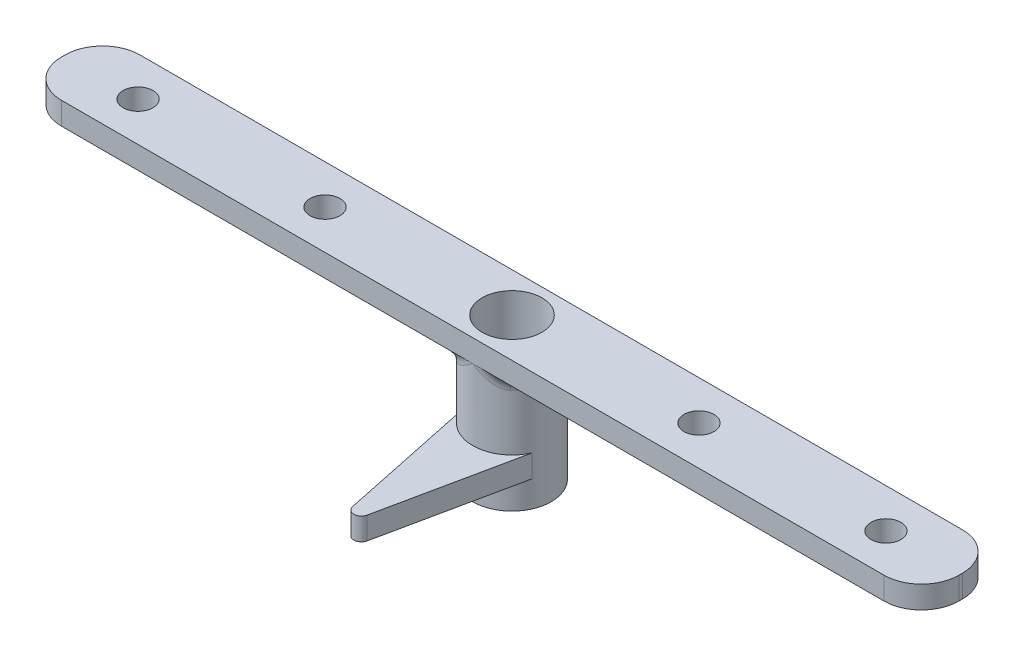
SolidWorks part; units mm, degrees
ref_plane "Front Plane" through (0, 0, 0) normal (0, 0, 1) x (1, 0, 0)
ref_plane "Top Plane" through (0, 0, 0) normal (0, 1, 0) x (1, 0, 0)
ref_plane "Right Plane" through (0, 0, 0) normal (1, 0, 0) x (0, 0, -1)
sketch "Sketch2" plane through (0, 0, 0) normal (1, 0, 0) x (0, 0, -1)
  line L0 (0, 0) -> (5.25, 0)
  line L1 (5.25, 0) -> (5.25, 16)
  line L2 (5.25, 16) -> (0, 16)
  line L3 (0, 16) -> (0, 0)
  dimension "D1" = 5.25
  dimension "D2" = 16
revolve "Revolve2" add sketch "Sketch2" angle 360 about L3
sketch "Sketch3" plane through (0, 0, 0) normal (0, -1, 0) x (1, 0, 0)
  line L0 (0, -5.25) -> (60, -5.25)
  line L1 (60, -5.25) -> (60, 5.25)
  line L2 (60, 5.25) -> (0, 5.25)
  line L3 (0, 5.25) -> (-60, 5.25)
  line L4 (-60, 5.25) -> (-60, -5.25)
  line L5 (-60, -5.25) -> (0, -5.25)
  circle A0 centre (0, 0) radius 5.25 construction
  dimension "D1" = 60
  dimension "D2" = 60
  dimension "D3" = 10.5
  dimension "D4" = 60
extrude "Boss-Extrude1" add sketch "Sketch3" against normal blind 3 from surface at -16 starting at face at (0, 16, 5.25)
fillet "Fillet4" radius 2 2 edges at (5.25, 16, 0) (-5.25, 16, 0)
fillet "Fillet7" radius 5 1 edges at (-60, 17.5, -5.25)
fillet "Fillet8" radius 5 1 edges at (-60, 17.5, 5.25)
fillet "Fillet9" radius 5 1 edges at (60, 17.5, 5.25)
fillet "Fillet10" radius 5 1 edges at (60, 17.5, -5.25)
sketch "Sketch8" plane through (0, 19, 0) normal (0, 1, 0) x (1, 0, 0)
  circle A0 centre (-25, 0) radius 2
  circle A1 centre (25, 0) radius 2
  dimension "D1" = 4
  dimension "D2" = 4
extrude "Cut-Extrude1" cut sketch "Sketch8" against normal through all
ref_plane "Plane1" through (0, 6.5, 0) normal (0, 1, 0) x (1, 0, 0)
sketch "Sketch13" plane through (0, 6.5, 0) normal (0, 1, 0) x (1, 0, 0)
  line L0 (-5.25, 0) -> (5.25, 0)
  line L1 (5.25, 0) -> (0, -25)
  line L2 (0, -25) -> (-5.25, 0)
  arc A0 (-3.6207, 3.8017) -> (-3.6207, -3.8017) centre (0, 0) ccw construction
  arc A1 (3.6207, -3.8017) -> (3.6207, 3.8017) centre (0, 0) ccw construction
  point P9 (14.5134, -25)
  dimension "D1" = 25
  dimension "D2" = 0
extrude "Boss-Extrude2" add sketch "Sketch13" against normal blind 3
hole_wizard "Hole1" positions "Sketch9" profile "Sketch10" legacy end condition through all
sketch "Sketch9" plane through (0, 19, 0) normal (0, 1, 0) x (1, 0, 0)
  point P0 (0, 0)
sketch "Sketch10" plane through (0, 19, 0) normal (1, 0, 0) x (0, 0, 1)
  line L0 (0, 0) -> (0, 19)
  line L1 (0, 19) -> (2.5, 19)
  line L2 (2.5, 19) -> (2.5, 12)
  line L3 (2.5, 12) -> (4, 12)
  line L4 (4, 12) -> (4, 0)
  line L5 (4, 0) -> (0, 0)
  line L6 (0, 110) -> (0, -10) construction
  dimension "Diameter" = 5
  dimension "Depth" = 19
  dimension "C-Bore Diameter" = 8
  dimension "C-Bore Depth" = 12
pattern_linear "LPattern1" count 2 spacing 25 along (1, 0, 0) count 2 spacing 25 along (-1, 0, 0) of "Cut-Extrude1"
fillet "Fillet12" radius 1 1 edges at (0, 5, 25)
